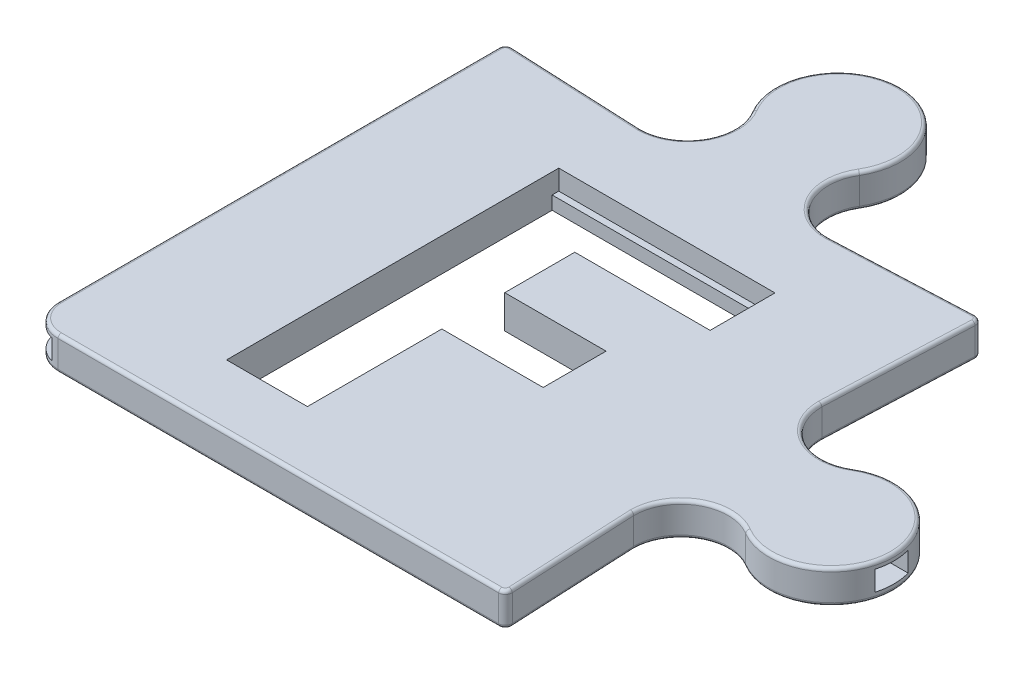
SolidWorks part; units mm, degrees
ref_plane "Front Plane" through (0, 0, 0) normal (0, 0, 1) x (1, 0, 0)
ref_plane "Top Plane" through (0, 0, 0) normal (0, 1, 0) x (1, 0, 0)
ref_plane "Right Plane" through (0, 0, 0) normal (1, 0, 0) x (0, 0, -1)
sketch "Sketch1" plane through (0, 0, 0) normal (0, 1, 0) x (1, 0, 0)
  line L0 (-31, -36) -> (37, -36) construction
  line L1 (-36, 37) -> (-36, -31) construction
  line L2 (-14.1421, 36) -> (-36, 37) construction
  line L3 (37, 37) -> (14.1421, 36) construction
  line L4 (36, 13.1421) -> (37, 37) construction
  line L5 (37, -36) -> (36, -15.1421) construction
  line L6 (-35.4, 36.3719) -> (-35.4, -31)
  line L7 (-36, 36) -> (36, 36) construction
  line L8 (-36, 36) -> (-36, -36) construction
  line L9 (-36, -36) -> (36, -36) construction
  line L10 (36, 36) -> (36, -36) construction
  line L11 (-31, -35.4) -> (36.3705, -35.4)
  line L12 (36.3705, -35.4) -> (35.4, -15.1568)
  line L13 (35.4, 13.155) -> (36.3732, 36.372)
  line L14 (36.3732, 36.372) -> (14.1555, 35.4)
  line L15 (-14.1562, 35.4) -> (-35.4, 36.3719)
  line L16 (-30, -24) -> (30, -24) construction
  line L17 (-30, 29) -> (30, 29) construction
  line L18 (-30, 29) -> (-30, -31) construction
  line L19 (-30, -31) -> (30, -31) construction
  line L20 (30, 29) -> (30, -31) construction
  line L21 (-30, 24) -> (30, 24) construction
  line L22 (-30, 24) -> (-30, -26) construction
  line L23 (-30, -26) -> (30, -26) construction
  line L24 (30, 24) -> (30, -26) construction
  arc A0 (-36, -31) -> (-31, -36) centre (-31, -31) ccw construction
  arc A1 (-14.1421, 36) -> (-8.571, 45.8485) centre (-14.1421, 42.5) ccw construction
  arc A2 (8.571, 45.8485) -> (-8.571, 45.8485) centre (0, 51) ccw construction
  arc A3 (8.571, 45.8485) -> (14.1421, 36) centre (14.1421, 42.5) ccw construction
  arc A4 (36, 13.1421) -> (45.8485, 7.571) centre (42.5, 13.1421) ccw construction
  arc A5 (45.8485, -9.571) -> (45.8485, 7.571) centre (51, -1) ccw construction
  arc A6 (45.8485, -9.571) -> (36, -15.1421) centre (42.5, -15.1421) ccw construction
  arc A7 (-35.4, -31) -> (-31, -35.4) centre (-31, -31) ccw
  arc A8 (46.1576, -9.0567) -> (35.4, -15.1568) centre (42.5, -15.1421) ccw
  arc A9 (46.1576, -9.0567) -> (46.1576, 7.0567) centre (51, -1) ccw
  arc A10 (35.4, 13.155) -> (46.1576, 7.0567) centre (42.5, 13.1421) ccw
  arc A11 (8.0567, 46.1576) -> (14.1555, 35.4) centre (14.1421, 42.5) ccw
  arc A12 (8.0567, 46.1576) -> (-8.0567, 46.1576) centre (0, 51) ccw
  arc A13 (-14.1562, 35.4) -> (-8.0567, 46.1576) centre (-14.1421, 42.5) ccw
  point P32 (36, 0)
  point P34 (0, 36)
  dimension "D5" = 6.5
  dimension "D6" = 10
  dimension "D7" = 6.5
  dimension "D13" = 5
  dimension "D9" = 10
  dimension "D11" = 6.5
  dimension "D12" = 6.5
  dimension "D1" = 72
  dimension "D2" = 1
  dimension "D3" = 1
  dimension "D4" = 15
  dimension "D8" = 1
  dimension "D10" = 35
  dimension "D14" = 15
  dimension "D15" = 36
  dimension "D16" = 1
  dimension "D18" = 60
  dimension "D19" = 60
  dimension "D20" = 5
  dimension "D21" = 6
  dimension "D22" = 5
  dimension "D23" = 50
  dimension "D24" = 2
  dimension "D17" = 0.6
extrude "Boss-Extrude1" add sketch "Sketch1" along normal blind 5
sketch "Sketch6" plane through (0, 0, 0) normal (0, -1, 0) x (1, 0, 0)
  line L0 (-35.4, -36.3719) -> (-35.4, 31) construction
  line L1 (-35.4, 17.9) -> (-27.4, 17.9)
  line L2 (-35.4, 17.9) -> (-35.4, -16.1)
  line L3 (-35.4, -16.1) -> (-27.4, -16.1)
  line L4 (-27.4, 17.9) -> (-27.4, -16.1)
  line L5 (-31, 35.4) -> (36.3705, 35.4) construction
  line L6 (-35.4, 14.65) -> (-30.4, 14.65)
  line L7 (-35.4, 14.65) -> (-35.4, -12.85)
  line L8 (-35.4, -12.85) -> (-30.4, -12.85)
  line L9 (-30.4, 14.65) -> (-30.4, -12.85)
  point P15 (-27.4, 0.9)
  point P16 (-30.4, 0.9)
  line M28 (-35.4, 31) -> (-35.4, -36.3719)
  dimension "D1" = 8
  dimension "D2" = 20.75
  dimension "D3" = 27.5
  dimension "D4" = 5
  dimension "D5" = 34
extrude "Cut-Extrude3" cut sketch "Sketch6" against normal blind 3 from offset 1 contours L6 L9 L8 L3 L4 L1 M28 | L9 L6 L2 L8 region at (-29.8665, 0, 0.9) region at (-32.9, 0, 0.9) offset against normal yes
extrude "Cut-Extrude4" cut sketch "Sketch6<3>" against normal up to next contours L9 L6 L2 L8 region at (-32.9, 0, 0.9)
sketch "Sketch6<3>" plane through (0, 0, 0) normal (0, -1, 0) x (1, 0, 0) same geometry as "Sketch6"
sketch "Sketch8" plane through (0, 0, 0) normal (0, -1, 0) x (1, 0, 0)
  line L1 (-2.5, -51.4) -> (2.5, -51.4)
  line L2 (-2.5, -51.4) -> (-2.5, -60.4)
  line L3 (-2.5, -60.4) -> (2.5, -60.4)
  line L4 (2.5, -51.4) -> (2.5, -60.4)
  line L5 (51.4, 3.5) -> (60.4, 3.5)
  line L6 (51.4, 3.5) -> (51.4, -1.5)
  line L7 (51.4, -1.5) -> (60.4, -1.5)
  line L8 (60.4, 3.5) -> (60.4, -1.5)
  arc A0 (-8.0567, -46.1576) -> (8.0567, -46.1576) centre (0, -51) ccw construction
  arc A1 (46.1576, -7.0567) -> (46.1576, 9.0567) centre (51, 1) ccw construction
  point P4 (0, -60.4)
  point P13 (60.4, 1)
  dimension "D1" = 5
  dimension "D2" = 9
  dimension "D3" = 5
  dimension "D4" = 9
extrude "Cut-Extrude5" cut sketch "Sketch8" against normal blind 3 from offset 1 offset against normal yes
sketch "Sketch9" plane through (0, 0, 0) normal (0, -1, 0) x (1, 0, 0)
  line L0 (-31, 35.4) -> (36.3705, 35.4) construction
  line L1 (-35.4, 14.65) -> (-35.4, 31) construction
  line L2 (-31.7636, 35.3332) -> (-35.4, 31) construction
  line L3 (-33.2571, 29.735) -> (-30.0429, 33.565) construction
  line L4 (-30.0429, 33.565) -> (-33.2571, 29.735) construction
  line L5 (-30.0429, 33.565) -> (-32.7119, 35.8048)
  line L6 (-33.2571, 29.735) -> (-35.926, 31.9747)
  line L7 (-32.7119, 35.8048) -> (-35.926, 31.9747)
  circle A0 centre (-31.65, 31.65) radius 2.5
  arc A1 (-31, 35.4) -> (-35.4, 31) centre (-31, 31) ccw construction
  arc M41 (-31, 35.4) -> (-35.4, 31) centre (-31, 31) ccw
  dimension "D1" = 5
  dimension "D3" = 3.75
  dimension "D4" = 5.6569
  dimension "D2" = 3.75
extrude "Cut-Extrude6" cut sketch "Sketch9" against normal blind 3 from offset 1 contours A0 L5 L6 M41 | A0 L5 region at (-33.6239, 0, 33.3064) region at (-31.65, 0, 31.65) offset against normal yes
sketch "Sketch11" plane through (-35.4, 0, 0) normal (-1, 0, 0) x (0, 0, 1)
  line L0 (-13.155, 0) -> (-36.372, 0) construction
  line L1 (-25.1, 3) -> (-19.1, 3)
  line L2 (-25.1, 3) -> (-25.1, 1.5)
  line L3 (-25.1, 1.5) -> (-19.1, 1.5)
  line L4 (-19.1, 3) -> (-19.1, 1.5)
  line L5 (-16.1, 4) -> (-16.1, 1) construction
  line L6 (35.4, 0) -> (15.1568, 0) construction
  line L7 (20.9, 3) -> (26.9, 3)
  line L8 (20.9, 3) -> (20.9, 1.5)
  line L9 (20.9, 1.5) -> (26.9, 1.5)
  line L10 (26.9, 3) -> (26.9, 1.5)
  line L12 (17.9, 4) -> (17.9, 1) construction
  dimension "D1" = 3
  dimension "D2" = 1.5
  dimension "D3" = 3
  dimension "D4" = 6
  dimension "D5" = 3
  dimension "D6" = 1.5
  dimension "D7" = 6
  dimension "D8" = 3
fillet "Fillet1" radius 0.5 17 edges at (-35.4, 0, 22.825) (-34.1113, 0, 34.1113) (2.6853, 0, 35.4) (35.8853, 0, 25.2784) (38.9978, 0, 8.966) (60.4, 0, 1) (38.9986, 0, -6.9655) (35.8866, 0, -24.7635) (25.2643, 0, -35.886) (7.9657, 0, -38.9984) (0, 0, -60.4) (-7.9658, 0, -38.9981) (-24.7781, 0, -35.886) (-35.4, 0, -24.611) (-32.9, 0, -12.85) (-30.4, 0, 0.9) (-32.9, 0, 14.65)
fillet "Fillet2" radius 0.5 13 edges at (-7.9658, 5, -38.9981) (0, 5, -60.4) (7.9657, 5, -38.9984) (25.2643, 5, -35.886) (35.8866, 5, -24.7635) (38.9986, 5, -6.9655) (60.4, 5, 1) (38.9978, 5, 8.966) (35.8853, 5, 25.2784) (2.6853, 5, 35.4) (-34.1113, 5, 34.1113) (-35.4, 5, -2.686) (-24.7781, 5, -35.886)
fillet "Fillet3" radius 1 9 edges at (36.2202, 0.1464, -36.2187) (36.2202, 4.8536, -36.2187) (36.3732, 2.5, -36.372) (-35.2536, 0.1464, -36.2186) (-35.2536, 4.8536, -36.2186) (36.2169, 0.1464, 35.2536) (36.2169, 4.8536, 35.2536) (36.3705, 2.5, 35.4) (-35.4, 2.5, -36.3719)
extrude "Cut-Extrude9" cut sketch "Sketch11" against normal blind 3
chamfer "Chamfer1" distance 1 angle 50 2 edges at (-35.4, 1.5, 23.9) (-35.4, 1.5, -22.1) first distance on face at (-35.4, 2.25, -22.1)
sketch "Sketch12" plane through (0, 5, 0) normal (0, 1, 0) x (1, 0, 0)
  text T0 "F" font "Poppins" height 50
extrude "Cut-Extrude10" cut sketch "Sketch12" against normal through all
sketch "Sketch13" plane through (0, 0, 0) normal (0, -1, 0) x (1, 0, 0)
  line L0 (-2.8648, 5.7712) -> (-2.8648, 26) construction
  line L1 (-15.035, 26) -> (-2.8648, 26)
  line L2 (-15.035, 26) -> (-15.035, 25)
  line L3 (-15.035, 25) -> (-2.8648, 25)
  line L4 (-2.8648, 26) -> (-2.8648, 25)
  line L5 (-2.8648, -3.6991) -> (12.3866, -3.6991) construction
  line L6 (12.3866, 5.7712) -> (11.3866, 5.7712)
  line L7 (12.3866, 5.7712) -> (12.3866, -3.6991)
  line L8 (12.3866, -3.6991) -> (11.3866, -3.6991)
  line L9 (11.3866, 5.7712) -> (11.3866, -3.6991)
  line L10 (-15.035, 26) -> (-15.035, -24) construction
  line L11 (-15.035, -23) -> (17.5082, -23)
  line L12 (-15.035, -23) -> (-15.035, -24)
  line L13 (-15.035, -24) -> (17.5082, -24)
  line L14 (17.5082, -23) -> (17.5082, -24)
  dimension "D1" = 1
  dimension "D2" = 1
  dimension "D3" = 1
extrude "Boss-Extrude2" add sketch "Sketch13" against normal blind 2
